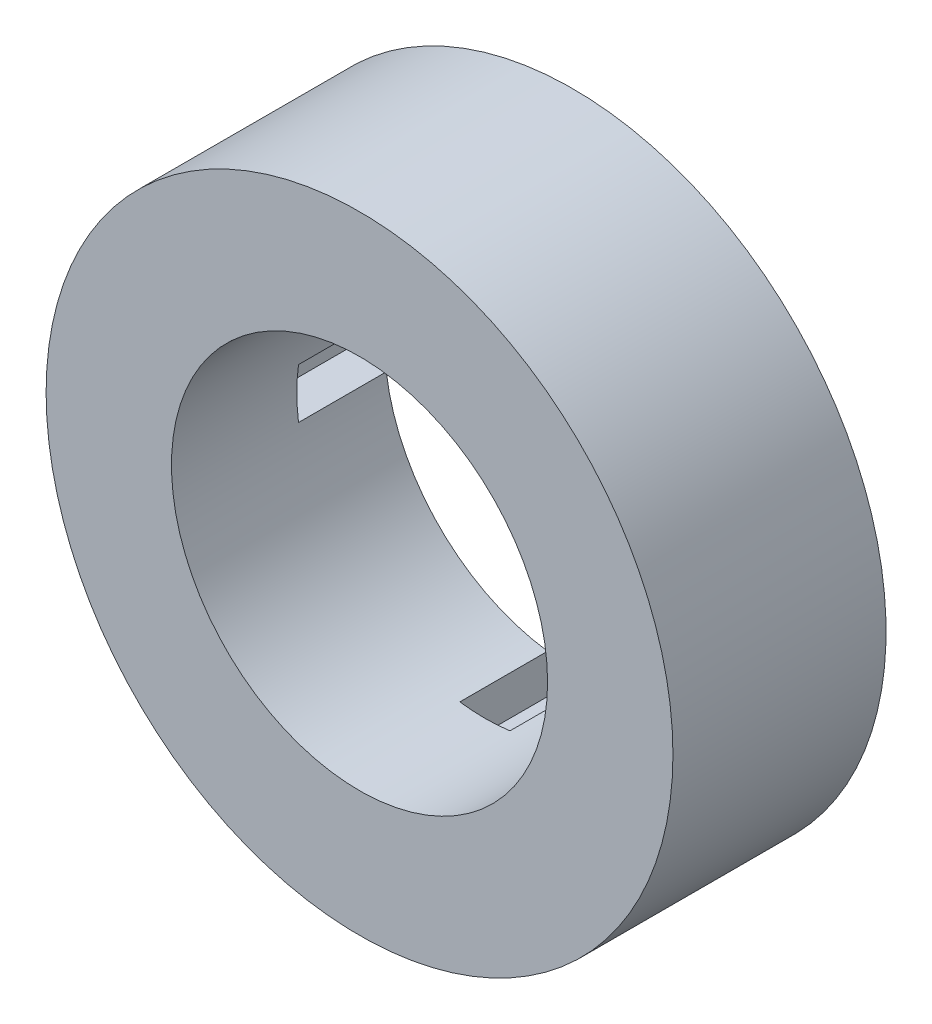
SolidWorks part; units mm, degrees
ref_plane "Ön Düzlem" through (0, 0, 0) normal (0, 0, 1) x (1, 0, 0)
ref_plane "Üst Düzlem" through (0, 0, 0) normal (0, 1, 0) x (1, 0, 0)
ref_plane "Sağ Düzlem" through (0, 0, 0) normal (1, 0, 0) x (0, 0, -1)
sketch "Sketch1" plane through (0, 0, 0) normal (0, 0, 1) x (1, 0, 0)
  circle A0 centre (0, 0) radius 3.75
  circle A1 centre (0, 0) radius 6.25
  dimension "D1" = 7.5
  dimension "D2" = 12.5
extrude "Boss-Extrude1" add sketch "Sketch1" along normal blind 5
sketch "Sketch2" plane through (0, 0, 0) normal (0, 0, -1) x (-1, 0, 0)
  circle A0 centre (0, 0) radius 3.75
  circle A1 centre (0, 0) radius 5.5
  dimension "D1" = 11
  dimension "D2" = 7.5
extrude "Boss-Extrude2" add sketch "Sketch2" along normal blind 3
thread "Thread1" pitch 0.6 method cut profile "Thread Profile1" start angle 0, offset 1, length 4, pitch 0.6, diameter 11
ref_plane "Plane1" through (5.5, 0, -4) normal (0, -1, 0) x (1, 0, 0)
sketch "Thread Profile1" plane through (5.5, 0, -4) normal (0, -1, 0) x (1, 0, 0)
  line L0 (0, 0) -> (0, 0.6) construction
  line L11 (0, 0) -> (0, 0.525)
  line L12 (0, 0.525) -> (-0.3248, 0.3375)
  line L13 (-0.3248, 0.3375) -> (-0.3248, 0.1875)
  line L15 (-0.3248, 0.1875) -> (0, 0)
  line L17 (-0.3248, 0.2625) -> (0, 0.2625) construction
  point P2 (0, 0)
  dimension "Pitch" = 0.6
  dimension "Profile_Angle" = 60
  dimension "Profile_Land" = 0.15
  dimension "Profile_Height" = 0.3248
sketch "Sketch5" plane through (0, 0, -3) normal (0, 0, -1) x (-1, 0, 0)
  line L0 (4.5, 0.5) -> (3.5, 0.5)
  line L1 (-0.5, 4.5) -> (0.5, 4.5)
  line L2 (-0.5, 4.5) -> (-0.5, 3.5)
  line L3 (-0.5, 3.5) -> (0.5, 3.5)
  line L4 (0.5, 4.5) -> (0.5, 3.5)
  line L5 (4.5, 0.5) -> (4.5, -0.5)
  line L6 (4.5, -0.5) -> (3.5, -0.5)
  line L7 (3.5, 0.5) -> (3.5, -0.5)
  line L8 (0.5, -4.5) -> (0.5, -3.5)
  line L9 (0.5, -4.5) -> (-0.5, -4.5)
  line L10 (-0.5, -4.5) -> (-0.5, -3.5)
  line L11 (0.5, -3.5) -> (-0.5, -3.5)
  line L12 (-4.5, -0.5) -> (-3.5, -0.5)
  line L13 (-4.5, -0.5) -> (-4.5, 0.5)
  line L14 (-4.5, 0.5) -> (-3.5, 0.5)
  line L15 (-3.5, -0.5) -> (-3.5, 0.5)
  point P4 (0, 3.5)
  point P21 (0, 0)
  dimension "D1" = 1
  dimension "D2" = 1
  dimension "D3" = 3.5
  dimension "D4" = 4
sketch "Sketch7" plane through (0, 0, -3) normal (0, 0, -1) x (-1, 0, 0)
  circle A0 centre (0, 0) radius 3.75
  circle A1 centre (0, 0) radius 5
  dimension "D1" = 7.5
  dimension "D2" = 10
extrude "Boss-Extrude3" add sketch "Sketch7" along normal blind 1.25
extrude "Cut-Extrude3" cut sketch "Sketch5" against normal blind 5.5 and the other way blind 6.5
sketch "Sketch8" plane through (0, 0, -4.25) normal (0, 0, -1) x (-1, 0, 0)
  circle A0 centre (0, 0) radius 3
  circle A1 centre (0, 0) radius 5
  dimension "D1" = 10
  dimension "D2" = 6
extrude "Boss-Extrude4" add sketch "Sketch8" along normal blind 0.5
sketch "Sketch9" plane through (0, 0, 0) normal (0, 1, 0) x (1, 0, 0)
  line L0 (6.25, 0) -> (-6.25, 0) construction
  line L1 (-9.219, 5.0608) -> (9.2004, 5.0608)
  line L2 (-9.219, 5.0608) -> (-9.219, -0.75)
  line L3 (-9.219, -0.75) -> (9.2004, -0.75)
  line L4 (9.2004, 5.0608) -> (9.2004, -0.75)
  dimension "D1" = 0.75
extrude "Cut-Extrude4" cut sketch "Sketch9" against normal blind 10 and the other way blind 10
sketch "Sketch10" plane through (0, 0, 0.75) normal (0, 0, -1) x (-1, 0, 0)
  line L0 (-3.5355, 3.5355) -> (0, 0) construction
  line L1 (0, 0) -> (-20, 0) construction
  circle A0 centre (-3.5355, 3.5355) radius 0.5
  dimension "D4" = 1
  dimension "D1" = 20
  dimension "D2" = 5
  dimension "D3" = 45
extrude "Cut-Extrude5" cut sketch "Sketch10" against normal blind 2.5
pattern_circular "CirPattern1" count 4 over 360 about axis through (0, 0, 5) along (0, 0, -1) of "Cut-Extrude5"
